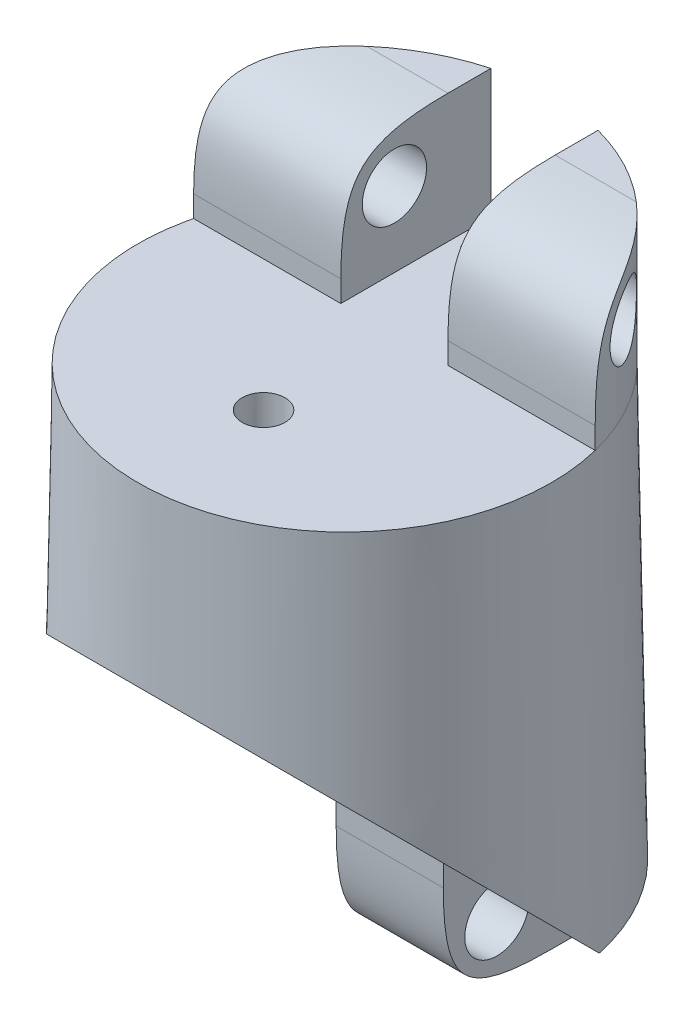
SolidWorks part; units mm, degrees
material "ABS"
ref_plane "Front Plane" through (0, 0, 0) normal (0, 0, 1) x (1, 0, 0)
ref_plane "Top Plane" through (0, 0, 0) normal (0, 1, 0) x (1, 0, 0)
ref_plane "Right Plane" through (0, 0, 0) normal (1, 0, 0) x (0, 0, -1)
sketch "Sketch1" plane through (0, 0, 0) normal (0, 1, 0) x (1, 0, 0)
  circle A0 centre (0, 0) radius 10
  dimension "D1" = 20
extrude "Boss-Extrude1" add sketch "Sketch1" along normal blind 20 draft 1 and the other way blind 6 draft 1
sketch "Sketch2" plane through (0, 0, 0) normal (1, 0, 0) x (0, 0, -1)
  line L0 (2.1047, -6) -> (2.1047, 0)
  line L1 (-10.1047, -6) -> (10.1047, -6) construction
  line L2 (2.1047, 0) -> (-12.1199, 14.2246)
  line L4 (-12.1199, 14.2246) -> (-12.1199, -6)
  line L5 (-12.1199, -6) -> (2.1047, -6)
  dimension "D1" = 8
  dimension "D2" = 135
  dimension "D3" = 6
extrude "Cut-Extrude1" cut sketch "Sketch2" against normal through all both and the other way through all
sketch "Sketch3" plane through (0, 0, -2.1047) normal (0, 0, 1) x (1, 0, 0)
  line L0 (-9.776, 0) -> (9.776, 0) construction
  line L1 (-2.5, 0) -> (2.5, 0)
  line L2 (-2.5, 0) -> (-2.5, -6)
  line L3 (-2.5, -6) -> (2.5, -6)
  line L4 (2.5, 0) -> (2.5, -6)
  line L5 (9.8831, -6) -> (-9.8831, -6) construction
  line L8 (11.399, -6) -> (-10.9058, -6)
  line L9 (11.399, -6) -> (11.399, 0)
  line L10 (11.399, 0) -> (-10.9058, 0)
  line L11 (-10.9058, -6) -> (-10.9058, 0)
  point P8 (0, 0)
  dimension "D1" = 5
  dimension "D2" = 0
extrude "Cut-Extrude2" cut sketch "Sketch3" against normal through all
sketch "Sketch4" plane through (2.5, 0, 0) normal (1, 0, 0) x (0, 0, -1)
  circle A0 centre (4.6047, -3.5) radius 1.5
  dimension "D1" = 2.5
  dimension "D2" = 2.5
extrude "Cut-Extrude3" cut sketch "Sketch4" against normal blind 20
fillet "Fillet1" radius 5 1 edges
sketch "Sketch5" plane through (0, 20, 0) normal (0, 1, 0) x (1, 0, 0)
  line L0 (-2.5, 9.3215) -> (-2.5, 2.3215)
  line L1 (-9.3675, 2.3215) -> (9.3675, 2.3215)
  line L2 (2.5, 2.3215) -> (2.5, 9.3215)
  circle A0 centre (0, 0) radius 9.6509 construction
  circle A1 centre (0, 0) radius 9.6509
  dimension "D1" = 5
  dimension "D2" = 7
extrude "Boss-Extrude2" add sketch "Sketch5" along normal blind 6
sketch "Sketch6" plane through (2.5, 0, 0) normal (-1, 0, 0) x (0, 0, 1)
  circle A0 centre (-4.8215, 23.5) radius 1.5
  dimension "D1" = 2.5
  dimension "D2" = 2.5
extrude "Cut-Extrude4" cut sketch "Sketch6" against normal through all both and the other way through all
fillet "Fillet2" radius 5 2 edges at (5.9338, 26, -2.3215) (-5.9338, 26, -2.3215)
sketch "Sketch7" plane through (0, 20, 0) normal (0, 1, 0) x (1, 0, 0)
  circle A0 centre (0, -3.7833) radius 1
  point P3 (0, 0)
extrude "Cut-Extrude5" cut sketch "Sketch7" against normal through all contours A0
sketch "Sketch8" plane through (0, 20, 0) normal (0, 1, 0) x (1, 0, 0)
  line L12 (2, 2.3215) -> (2.1996, 2.2857)
  line L13 (2, 2.3215) -> (2, 8.9297)
  line L14 (-2, 8.9297) -> (-2, 2.3215)
  line L15 (2, 7.4024) -> (2, 8.9297)
  line L16 (-2, 8.9297) -> (-2, 7.4024)
  line L17 (-2, 7.4024) -> (2, 7.4024)
  arc A8 (2, 8.9297) -> (-2, 8.9297) centre (0, 0) ccw
  arc A9 (2, 8.9297) -> (-2, 8.9297) centre (0, 0) ccw
  dimension "D1" = 0.5
extrude "Cut-Extrude6" cut sketch "Sketch8" against normal through all contours L15 A9 L16 L17
